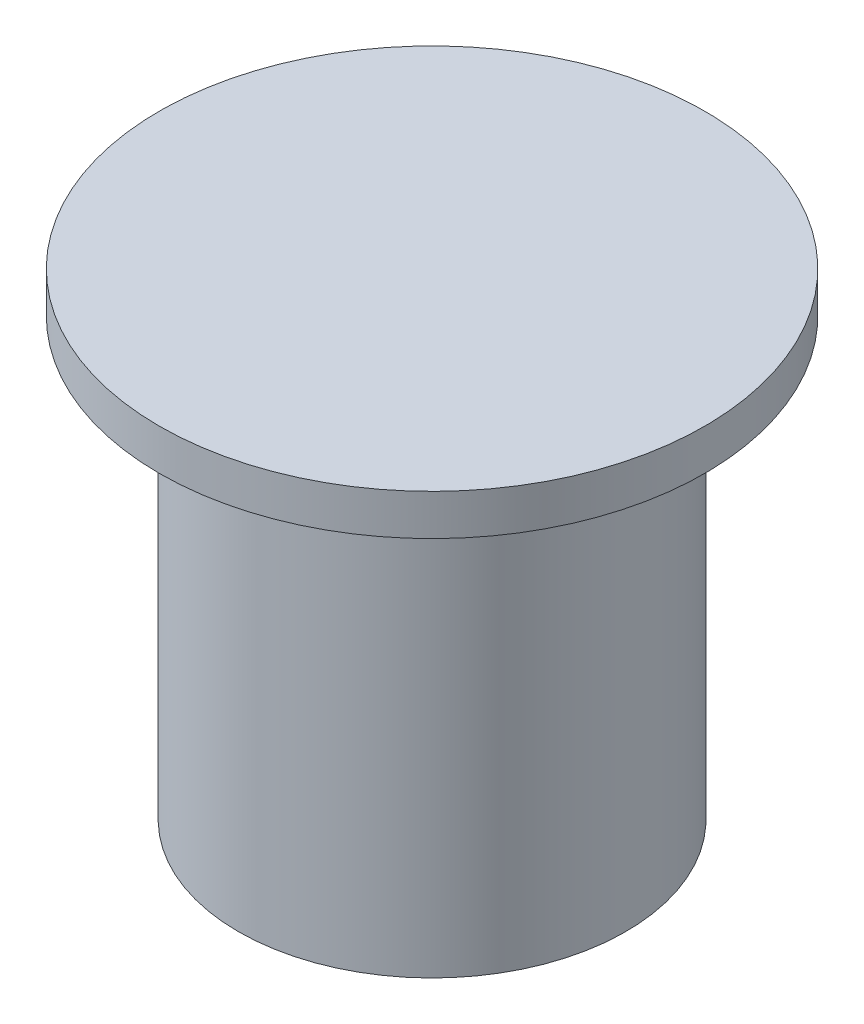
SolidWorks part; units mm, degrees
ref_plane "Front Plane" through (0, 0, 0) normal (0, 0, 1) x (1, 0, 0)
ref_plane "Top Plane" through (0, 0, 0) normal (0, 1, 0) x (1, 0, 0)
ref_plane "Right Plane" through (0, 0, 0) normal (1, 0, 0) x (0, 0, -1)
sketch "Sketch1" plane through (0, 0, 0) normal (0, 1, 0) x (1, 0, 0)
  circle A0 centre (0, 0) radius 7.1
extrude "Boss-Extrude1" add sketch "Sketch1" along normal blind 16
sketch "Sketch2" plane through (0, 16, 0) normal (0, 1, 0) x (1, 0, 0)
  circle A0 centre (0, 0) radius 10
extrude "Boss-Extrude2" add sketch "Sketch2" along normal blind 1.5
